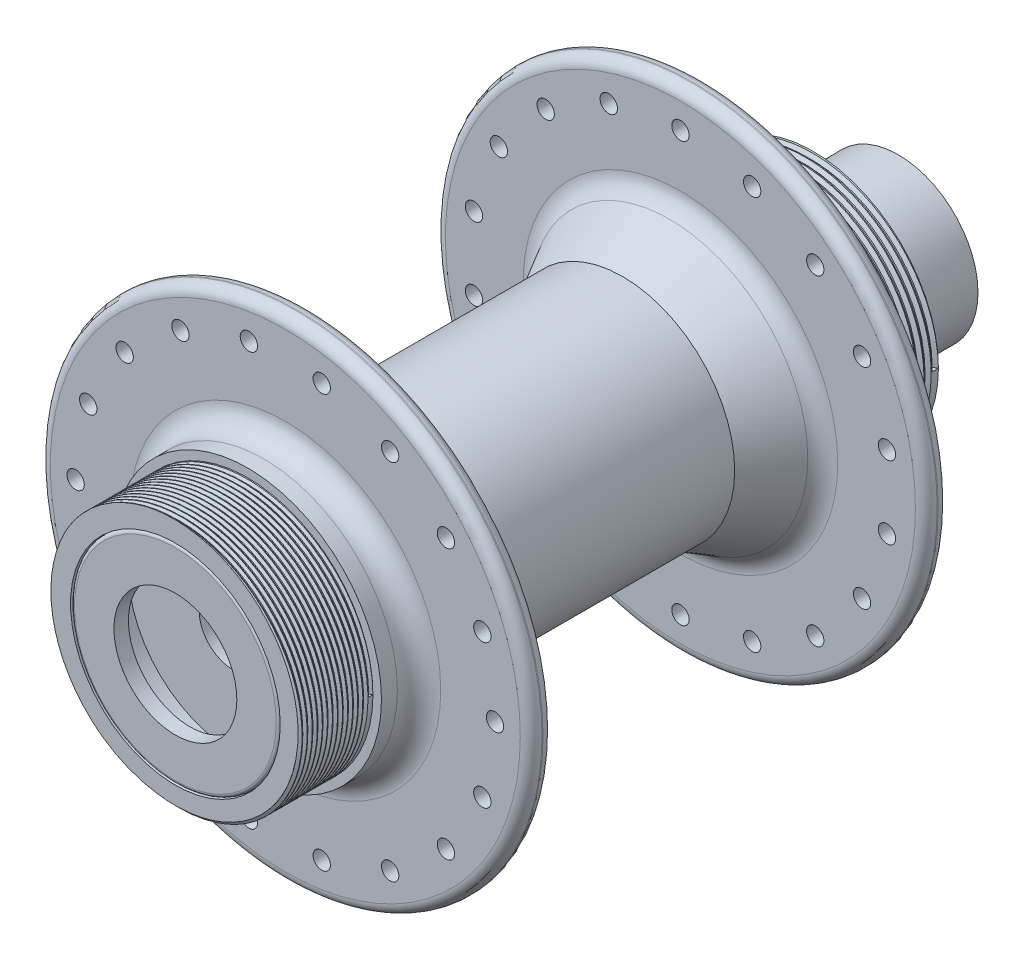
SolidWorks part; units mm, degrees
ref_plane "Front Plane" through (0, 0, 0) normal (0, 0, 1) x (1, 0, 0)
ref_plane "Top Plane" through (0, 0, 0) normal (0, 1, 0) x (1, 0, 0)
ref_plane "Right Plane" through (0, 0, 0) normal (1, 0, 0) x (0, 0, -1)
sketch "Sketch1" plane through (0, 0, 0) normal (1, 0, 0) x (0, 0, -1)
  line L0 (-77.7424, 0) -> (22.2576, 0) construction
  line L1 (-77.7424, 0) -> (-77.7424, 4.7) construction
  line L2 (22.2576, 11) -> (14.2576, 11) construction
  line L3 (-62.5424, 21.5) -> (-62.5424, 32.5)
  line L4 (-4.7424, 4.7) -> (-4.7424, 34) construction
  line L5 (-59.3924, 21.7545) -> (-59.3924, 32.5)
  line L6 (22.2576, 4.7) -> (22.2576, 11)
  line L7 (-77.7424, 4.7) -> (22.2576, 4.7)
  line L8 (-27.7424, 0) -> (-27.7424, 42.9514) construction
  line L9 (-61.0424, 34) -> (-60.8924, 34)
  line L10 (0.4576, 4.7) -> (0.4576, 17.325) construction
  line L11 (-59.3924, 24) -> (-7.8924, 24) construction
  line L12 (-33.6424, 24) -> (-33.6424, 15.5) construction
  line L13 (0.4576, 18.5) -> (-1.7424, 18.5)
  line L14 (-7.8924, 4.7) -> (-7.8924, 34) construction
  line L15 (-57.8632, 19.1398) -> (-51.3924, 15.5)
  line L16 (-15.8924, 15.5) -> (-7.8924, 15.5) construction
  line L17 (0.4576, 17.325) -> (0.4576, 18.5)
  line L18 (10.4576, 11.0125) -> (10.4576, 17.325)
  line L19 (10.4576, 17.325) -> (0.4576, 17.325)
  line L20 (-77.7424, 4.7) -> (-77.7424, 17.325)
  line L21 (10.4576, 11.0125) -> (22.2576, 11)
  line L26 (-7.8924, 21.7545) -> (-7.8924, 32.5)
  line L27 (-77.7424, 17.325) -> (-67.7424, 17.325)
  line L28 (-67.7424, 4.7) -> (-67.7424, 17.325) construction
  line L29 (-4.7424, 21.5) -> (-4.7424, 32.5)
  line L30 (-67.7424, 17.325) -> (-67.7424, 18.5)
  line L31 (-67.7424, 18.5) -> (-65.5424, 18.5)
  line L32 (-6.3924, 34) -> (-6.2424, 34)
  line L35 (-9.4216, 19.1398) -> (-15.8924, 15.5)
  line L42 (-59.3924, 12.7959) -> (-59.3924, 34) construction
  line L44 (-62.5424, 12.7959) -> (-62.5424, 34) construction
  line L45 (-51.3924, 15.5) -> (-15.8924, 15.5)
  arc A0 (-6.2424, 34) -> (-4.7424, 32.5) centre (-6.2424, 32.5) cw
  arc A1 (-6.3924, 34) -> (-7.8924, 32.5) centre (-6.3924, 32.5) ccw
  arc A2 (-1.7424, 18.5) -> (-4.7424, 21.5) centre (-1.7424, 21.5) cw
  arc A3 (-60.8924, 34) -> (-59.3924, 32.5) centre (-60.8924, 32.5) cw
  arc A4 (-61.0424, 34) -> (-62.5424, 32.5) centre (-61.0424, 32.5) ccw
  arc A5 (-57.8632, 19.1398) -> (-59.3924, 21.7545) centre (-56.3924, 21.7545) cw
  arc A7 (-9.4216, 19.1398) -> (-7.8924, 21.7545) centre (-10.8924, 21.7545) ccw
  arc A8 (-65.5424, 18.5) -> (-62.5424, 21.5) centre (-65.5424, 21.5) ccw
  point P3 (13.7576, 15.5)
  point P10 (-77.7424, 15)
  point P16 (32.1576, 15)
  point P19 (-4.7424, 34)
  point P44 (13.2576, 15.5)
  point P46 (-77.7424, 18)
  point P48 (22.2576, 18)
  point P54 (-77.7424, 15.5)
  point P55 (22.2576, 15.5)
  point P68 (-7.8924, 20)
  point P69 (13.3576, 15.5)
  point P70 (13.3576, 4.7)
  point P71 (13.7576, 13.5)
  point P72 (13.2576, 13.5)
  point P76 (-62.5424, 18.5)
  dimension "D17" = 8
  dimension "D23" = 5.2
  dimension "D12" = 1.5
  dimension "D4" = 1.5
  dimension "D6" = 51.5
  dimension "D9" = 20
  dimension "D10" = 17.325
  dimension "D8" = 20
  dimension "D37" = 3
  dimension "D24" = 3
  dimension "D1" = 100
  dimension "D5" = 8
  dimension "D7" = 3.15
  dimension "D11" = 4.7
  dimension "D13" = 10
  dimension "D14" = 11
  dimension "D15" = 18.5
  dimension "D34" = 34
  dimension "D35" = 3.15
revolve "Revolve1" add sketch "Sketch1" angle 360 about L0
thread "Thread1" pitch 0.7 method cut profile "Thread Profile1" start angle 0, offset 0, length 0, pitch 0.7, diameter 34.65
ref_plane "Plane4" through (17.325, 0, 67.7424) normal (0, -1, 0) x (1, 0, 0)
sketch "Thread Profile1" plane through (17.325, 0, 67.7424) normal (0, -1, 0) x (1, 0, 0)
  line L0 (0, 0) -> (0, 0.7) construction
  line L11 (0, 0) -> (0, 0.6125)
  line L12 (0, 0.6125) -> (-0.3789, 0.3937)
  line L13 (-0.3789, 0.3937) -> (-0.3789, 0.2187)
  line L15 (-0.3789, 0.2187) -> (0, 0)
  line L17 (-0.3789, 0.3062) -> (0, 0.3062) construction
  point P2 (0, 0)
  dimension "Pitch" = 0.7
  dimension "Profile_Angle" = 60
  dimension "Profile_Land" = 0.175
  dimension "Profile_Height" = 0.3789
ref_plane "Plane5" through (0, 0, 77.7424) normal (0, 0, 1) x (1, 0, 0)
sketch "Sketch27" plane through (0, 0, 77.7424) normal (0, 0, 1) x (1, 0, 0)
  circle A0 centre (0, 0) radius 14.5
  dimension "D1" = 29
extrude "Cut-Extrude1" cut sketch "Sketch27" against normal blind 8
ref_plane "Plane3" through (16, 0, 0) normal (1, 0, 0) x (0, 0, -1)
sketch "Sketch18" plane through (16, 0, 0) normal (1, 0, 0) x (0, 0, -1)
  line L0 (-51.3924, 0) -> (-15.8924, 0) construction
  line L5 (-51.3924, 15.5) -> (-51.3924, -15.5) construction
  line L6 (-15.8924, 15.5) -> (-15.8924, -15.5) construction
ref_plane "Plane6" through (0, 0, 77.7424) normal (0, 0, 1) x (1, 0, 0)
sketch "Sketch32" plane through (0, 0, 77.7424) normal (0, 0, 1) x (1, 0, 0)
  circle A0 centre (0, 0) radius 14.45
  circle A1 centre (0, 0) radius 8.5
  dimension "D1" = 28.9
  dimension "D2" = 17
extrude "Boss-Extrude1" add sketch "Sketch32" against normal blind 2 separate body
fillet "Fillet1" radius 0.5 1 edges at (14.45, 0, 77.7424)
ref_plane "Plane7" through (0, 0, -22.2576) normal (0, 0, -1) x (-1, 0, 0)
sketch "Sketch33" plane through (0, 0, -22.2576) normal (0, 0, -1) x (-1, 0, 0)
  circle A0 centre (0, 0) radius 8.5
  dimension "D1" = 17
extrude "Cut-Extrude2" cut sketch "Sketch33" against normal blind 6
ref_plane "Plane8" through (0, 0, 4.7424) normal (0, 0, -1) x (-1, 0, 0)
sketch "Sketch34" plane through (0, 0, 4.7424) normal (0, 0, -1) x (-1, 0, 0)
  line L0 (0, 0) -> (0, 29) construction
  circle A0 centre (0, 0) radius 29 construction
  circle A1 centre (0, 29) radius 1.2
  circle A2 centre (-0.0001, 0.0003) radius 29 construction
  circle A3 centre (9.9185, 27.2514) radius 1.2
  circle A4 centre (0, 0.0007) radius 29 construction
  circle A5 centre (18.6408, 22.216) radius 1.2
  circle A6 centre (0.0002, 0.001) radius 29 construction
  circle A7 centre (25.1149, 14.501) radius 1.2
  circle A8 centre (0.0004, 0.0012) radius 29 construction
  circle A9 centre (28.5599, 5.037) radius 1.2
  circle A10 centre (0.0008, 0.0013) radius 29 construction
  circle A11 centre (28.5602, -5.0345) radius 1.2
  circle A12 centre (0.0011, 0.0013) radius 29 construction
  circle A13 centre (25.1159, -14.4987) radius 1.2
  circle A14 centre (0.0014, 0.0012) radius 29 construction
  circle A15 centre (18.6423, -22.2141) radius 1.2
  circle A16 centre (0.0017, 0.001) radius 29 construction
  circle A17 centre (9.9203, -27.2501) radius 1.2
  circle A18 centre (0.0019, 0.0007) radius 29 construction
  circle A19 centre (0.0019, -28.9993) radius 1.2
  circle A20 centre (0.0019, 0.0003) radius 29 construction
  circle A21 centre (-9.9166, -27.2507) radius 1.2
  circle A22 centre (0.0019, 0) radius 29 construction
  circle A23 centre (-18.639, -22.2153) radius 1.2
  circle A24 centre (0.0017, -0.0003) radius 29 construction
  circle A25 centre (-25.113, -14.5003) radius 1.2
  circle A26 centre (0.0014, -0.0005) radius 29 construction
  circle A27 centre (-28.558, -5.0363) radius 1.2
  circle A28 centre (0.0011, -0.0006) radius 29 construction
  circle A29 centre (-28.5583, 5.0352) radius 1.2
  circle A30 centre (0.0008, -0.0006) radius 29 construction
  circle A31 centre (-25.114, 14.4994) radius 1.2
  circle A32 centre (0.0004, -0.0005) radius 29 construction
  circle A33 centre (-18.6404, 22.2148) radius 1.2
  circle A34 centre (0.0002, -0.0003) radius 29 construction
  circle A35 centre (-9.9184, 27.2508) radius 1.2
  point P76 (0.0009, 0.0003)
  dimension "D1" = 58
  dimension "D2" = 2.4
  dimension "D3" = 18
extrude "Cut-Extrude3" cut sketch "Sketch34" against normal blind 10
ref_plane "Plane9" through (0, 0, 62.5424) normal (0, 0, 1) x (1, 0, 0)
sketch "Sketch35" plane through (0, 0, 62.5424) normal (0, 0, 1) x (1, 0, 0)
  line L0 (0, 0) -> (0, 29) construction
  line L1 (0, 0) -> (5.0358, 28.5594) construction
  circle A0 centre (0, 0) radius 29 construction
  circle A1 centre (5.0358, 28.5594) radius 1.2
  circle A2 centre (-0.0001, 0.0003) radius 29 construction
  circle A3 centre (14.4999, 25.1151) radius 1.2
  circle A4 centre (0, 0.0007) radius 29 construction
  circle A5 centre (22.2153, 18.6415) radius 1.2
  circle A6 centre (0.0002, 0.001) radius 29 construction
  circle A7 centre (27.2513, 9.9196) radius 1.2
  circle A8 centre (0.0004, 0.0012) radius 29 construction
  circle A9 centre (29.0004, 0.0012) radius 1.2
  circle A10 centre (0.0008, 0.0013) radius 29 construction
  circle A11 centre (27.2519, -9.9173) radius 1.2
  circle A12 centre (0.0011, 0.0013) radius 29 construction
  circle A13 centre (22.2164, -18.6395) radius 1.2
  circle A14 centre (0.0014, 0.0012) radius 29 construction
  circle A15 centre (14.5014, -25.1135) radius 1.2
  circle A16 centre (0.0017, 0.001) radius 29 construction
  circle A17 centre (5.0375, -28.5584) radius 1.2
  circle A18 centre (0.0019, 0.0007) radius 29 construction
  circle A19 centre (-5.0339, -28.5587) radius 1.2
  circle A20 centre (0.0019, 0.0003) radius 29 construction
  circle A21 centre (-14.4981, -25.1144) radius 1.2
  circle A22 centre (0.0019, 0) radius 29 construction
  circle A23 centre (-22.2134, -18.6408) radius 1.2
  circle A24 centre (0.0017, -0.0003) radius 29 construction
  circle A25 centre (-27.2494, -9.9189) radius 1.2
  circle A26 centre (0.0014, -0.0005) radius 29 construction
  circle A27 centre (-28.9986, -0.0005) radius 1.2
  circle A28 centre (0.0011, -0.0006) radius 29 construction
  circle A29 centre (-27.25, 9.9179) radius 1.2
  circle A30 centre (0.0008, -0.0006) radius 29 construction
  circle A31 centre (-22.2145, 18.6402) radius 1.2
  circle A32 centre (0.0004, -0.0005) radius 29 construction
  circle A33 centre (-14.4996, 25.1142) radius 1.2
  circle A34 centre (0.0002, -0.0003) radius 29 construction
  circle A35 centre (-5.0356, 28.5591) radius 1.2
  point P77 (0.0009, 0.0003)
  dimension "D1" = 58
  dimension "D3" = 2.4
  dimension "D2" = 10
  dimension "D4" = 18
extrude "Cut-Extrude4" cut sketch "Sketch35" against normal blind 10
thread "Thread2" pitch 1 method cut profile "Thread Profile2" start angle 0, offset 0, length 10, pitch 1, diameter 34.65
ref_plane "Plane10" through (17.325, 0, -10.4576) normal (0, -1, 0) x (1, 0, 0)
sketch "Thread Profile2" plane through (17.325, 0, -10.4576) normal (0, -1, 0) x (1, 0, 0)
  line L0 (0, 0) -> (0, 1) construction
  line L11 (0, 0) -> (0, 0.875)
  line L12 (0, 0.875) -> (-0.5413, 0.5625)
  line L13 (-0.5413, 0.5625) -> (-0.5413, 0.3125)
  line L15 (-0.5413, 0.3125) -> (0, 0)
  line L17 (-0.5413, 0.4375) -> (0, 0.4375) construction
  point P2 (0, 0)
  dimension "Pitch" = 1
  dimension "Profile_Angle" = 60
  dimension "Profile_Land" = 0.25
  dimension "Profile_Height" = 0.5413
